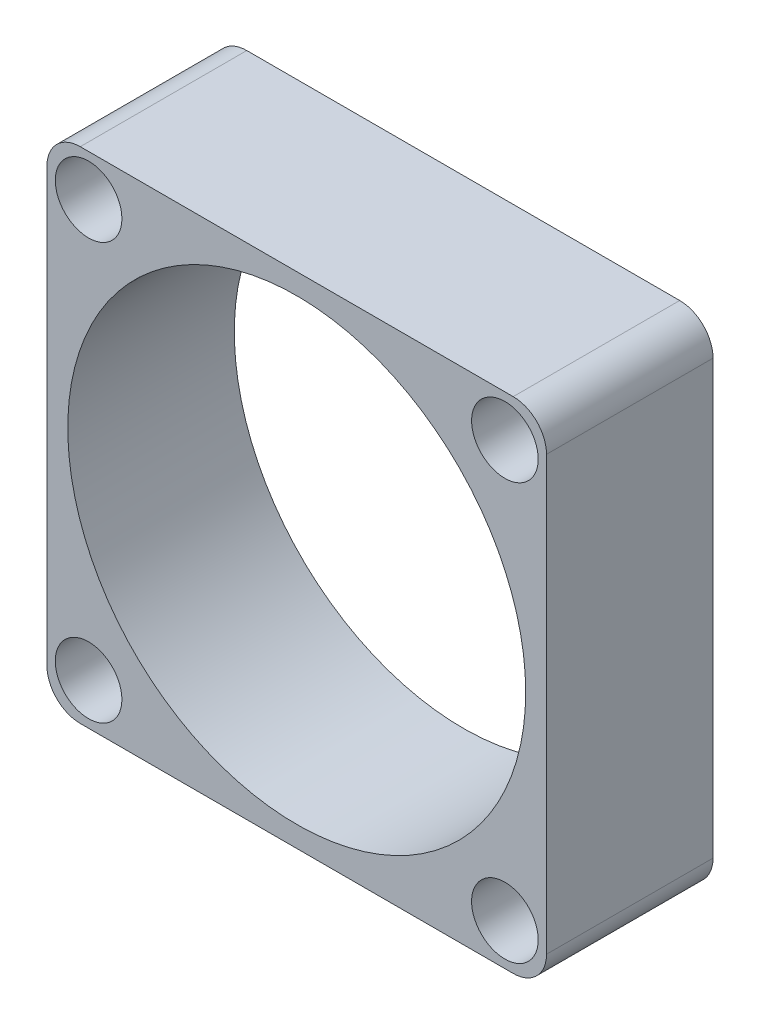
SolidWorks part; units mm, degrees
material "ABS PC"
ref_plane "Front Plane" through (0, 0, 0) normal (0, 0, 1) x (1, 0, 0)
ref_plane "Top Plane" through (0, 0, 0) normal (0, 1, 0) x (1, 0, 0)
ref_plane "Right Plane" through (0, 0, 0) normal (1, 0, 0) x (0, 0, -1)
sketch "Sketch1" plane through (0, 0, 0) normal (0, 0, 1) x (1, 0, 0)
  line L1 (0, 0) -> (30, 0)
  line L2 (0, 0) -> (0, 30)
  line L3 (0, 30) -> (30, 30)
  line L4 (30, 0) -> (30, 30)
  dimension "D1" = 30
  dimension "D2" = 30
extrude "Boss-Extrude1" add sketch "Sketch1" along normal blind 10
sketch "Sketch3" plane through (0, 0, 10) normal (0, 0, 1) x (1, 0, 0)
  line L0 (0, 15) -> (15, 15) construction
  line L1 (0, 30) -> (0, 0) construction
  line L2 (15, 15) -> (15, 0) construction
  line L3 (0, 0) -> (30, 0) construction
  circle A0 centre (15, 15) radius 13.75
  circle A1 centre (2.5, 27.5) radius 2
  circle A2 centre (27.5, 27.5) radius 2
  circle A3 centre (27.5, 2.5) radius 2
  circle A4 centre (2.5, 2.5) radius 2
  dimension "D1" = 27.5
  dimension "D6" = 4
  dimension "D2" = 25
  dimension "D3" = 25
  dimension "D4" = 25
  dimension "D5" = 25
extrude "Cut-Extrude1" cut sketch "Sketch3" against normal blind 10 contours A0 | A1 | A4 | A3 | A2 region at (15, 15, 10) region at (2.5, 27.5, 10) region at (27.5, 27.5, 10) region at (27.5, 2.5, 10) region at (2.5, 2.5, 10)
fillet "Fillet1" radius 2 4 edges at (0, 0, 5) (30, 0, 5) (0, 30, 5) (30, 30, 5)
